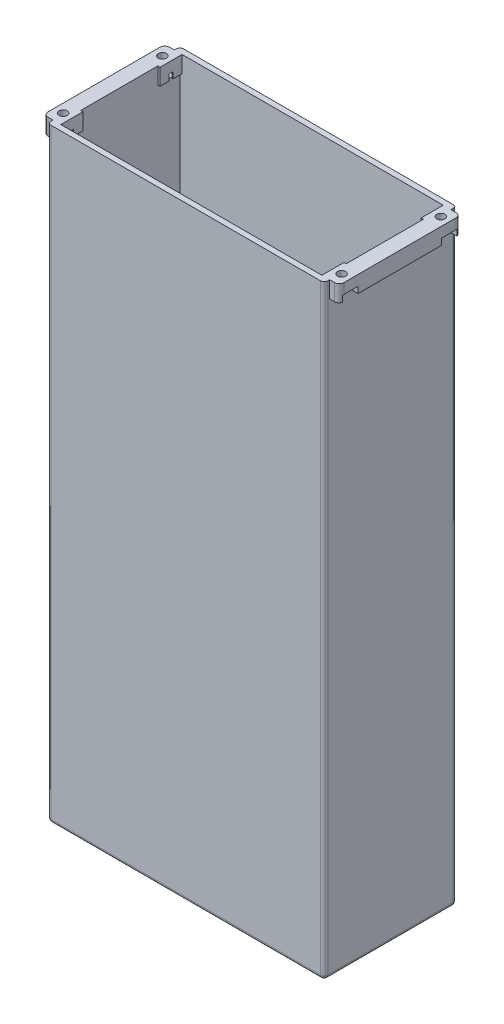
SolidWorks part; units mm, degrees
ref_plane "前视基准面" through (0, 0, 0) normal (0, 0, 1) x (1, 0, 0)
ref_plane "上视基准面" through (0, 0, 0) normal (0, 1, 0) x (1, 0, 0)
ref_plane "右视基准面" through (0, 0, 0) normal (1, 0, 0) x (0, 0, -1)
sketch "草图1" plane through (0, 0, 0) normal (0, 1, 0) x (1, 0, 0)
  line L1 (0, 0) -> (72, 0)
  line L2 (0, 0) -> (0, 32.9)
  line L3 (0, 32.9) -> (72, 32.9)
  line L4 (72, 0) -> (72, 32.9)
  dimension "D1" = 72
  dimension "D2" = 32.9
extrude "凸台-拉伸1" add sketch "草图1" along normal blind 162.5
shell "抽壳1" thickness 1.5
fillet "圆角2" radius 1 8 edges at (-1.5, 80.5, -34.4) (-1.5, 80.5, 1.5) (73.5, 80.5, 1.5) (73.5, 80.5, -34.4) (36, -1.5, 1.5) (-1.5, -1.5, -16.45) (73.5, -1.5, -16.45) (36, -1.5, -34.4)
sketch "草图2" plane through (0, 162.5, 0) normal (0, 1, 0) x (1, 0, 0)
  line L0 (0, 32.9) -> (0, 0) construction
  line L1 (-1.5, 6) -> (-1.5, 26.9)
  line L2 (-1.5, 33.4) -> (-1.5, -0.5) construction
  line L3 (0.6, 26.9) -> (-1.5, 26.9)
  line L4 (-4.1, 26.9) -> (-4.1, 6)
  line L5 (0.6, 26.9) -> (0.6, 32.9)
  line L6 (0.6, 32.9) -> (-4.1, 32.9)
  line L7 (-4.1, 26.9) -> (-4.1, 32.9)
  line L8 (0.6, 29.9) -> (-4.1, 29.9) construction
  line L9 (72, 32.9) -> (0, 32.9) construction
  line L10 (36, 0) -> (36, 32.9) construction
  line L11 (73.5, 26.9) -> (73.5, 6)
  line L12 (0, 0) -> (72, 0) construction
  line L13 (72, 16.45) -> (0, 16.45) construction
  line L14 (72, 0) -> (72, 32.9) construction
  line L15 (71.4, 32.9) -> (76.1, 32.9)
  line L16 (76.1, 26.9) -> (76.1, 32.9)
  line L17 (71.4, 26.9) -> (73.5, 26.9)
  line L18 (71.4, 26.9) -> (71.4, 32.9)
  line L19 (71.4, 6) -> (71.4, 0)
  line L20 (71.4, 6) -> (73.5, 6)
  line L21 (76.1, 6) -> (76.1, 0)
  line L22 (71.4, 0) -> (76.1, 0)
  line L23 (0.6, 0) -> (-4.1, 0)
  line L24 (-4.1, 6) -> (-4.1, 0)
  line L25 (0.6, 6) -> (-1.5, 6)
  line L26 (0.6, 6) -> (0.6, 0)
  line L27 (73.5, -0.5) -> (73.5, 33.4) construction
  line L28 (76.1, 6) -> (76.1, 26.9)
  point P30 (-1.75, 32.9)
  dimension "D2" = 4.7
  dimension "D1" = 0.6
  dimension "D3" = 6
  dimension "D4" = 3
extrude "凸台-拉伸2" add sketch "草图2" against normal blind 4.5
sketch "草图8" plane through (0, 162.5, 0) normal (0, 1, 0) x (1, 0, 0)
  line L0 (-1.5, 32.9) -> (-4.1, 32.9) construction
  line L3 (36, 32.9) -> (36, 0) construction
  line L4 (71.4, 32.9) -> (0.6, 32.9) construction
  line L5 (0.6, 0) -> (71.4, 0) construction
  line L6 (36, 16.45) -> (0, 16.45) construction
  line L7 (0, 26.9) -> (0, 6) construction
  line L8 (0.6, 26.9) -> (0.6, 32.9) construction
  line L14 (-1.75, 26.442) -> (-1.75, 33.4315) construction
  circle A0 centre (-1.75, 29.9) radius 1.1
  circle A1 centre (73.75, 29.9) radius 1.1
  circle A2 centre (73.75, 3) radius 1.1
  circle A3 centre (-1.75, 3) radius 1.1
  dimension "D1" = 2.2
  dimension "D2" = 3
  dimension "D3" = 2.35
extrude "切除-拉伸3" cut sketch "草图8" against normal blind 5
sketch "草图10" plane through (0, 158, 0) normal (0, -1, 0) x (1, 0, 0)
  line L0 (-2.3609, -27.8) -> (-4.3251, -27.8)
  line L2 (-2.4774, -32) -> (-0.5376, -32)
  line L3 (-0.5376, -32) -> (0.6749, -29.9)
  line L4 (0.6749, -29.9) -> (-0.5376, -27.8)
  line L5 (-0.5376, -27.8) -> (-2.3609, -27.8)
  line L7 (-4.0491, -30.1178) -> (-2.8944, -32.1178) [skipped]
  line L8 (-3.0882, -28.0178) -> (-4.2429, -30.0178) [skipped]
  line L9 (-4.3251, -27.8) -> (-4.3251, -32)
  line L10 (-4.3251, -32) -> (-2.4774, -32)
  line L11 (36, 0.5) -> (36, -33.4) construction
  line L12 (72.5, 0.5) -> (-0.5, 0.5) construction
  line L13 (-0.5, -33.4) -> (72.5, -33.4) construction
  line L14 (72.5, -16.45) -> (36, -16.45) construction
  line L15 (72.5, -33.4) -> (72.5, 0.5) construction
  line L16 (76.3251, -27.8) -> (76.3251, -32)
  line L17 (74.3609, -27.8) -> (76.3251, -27.8)
  line L18 (72.5376, -27.8) -> (74.3609, -27.8)
  line L19 (71.3251, -29.9) -> (72.5376, -27.8)
  line L20 (72.5376, -32) -> (71.3251, -29.9)
  line L21 (74.4774, -32) -> (72.5376, -32)
  line L22 (76.3251, -32) -> (74.4774, -32)
  line L23 (-4.3251, -5.1) -> (-4.3251, -0.9)
  line L24 (-2.3609, -5.1) -> (-4.3251, -5.1)
  line L25 (-0.5376, -5.1) -> (-2.3609, -5.1)
  line L26 (0.6749, -3) -> (-0.5376, -5.1)
  line L27 (-0.5376, -0.9) -> (0.6749, -3)
  line L28 (-2.4774, -0.9) -> (-0.5376, -0.9)
  line L29 (-4.3251, -0.9) -> (-2.4774, -0.9)
  line L30 (74.3609, -5.1) -> (76.3251, -5.1)
  line L31 (72.5376, -5.1) -> (74.3609, -5.1)
  line L32 (71.3251, -3) -> (72.5376, -5.1)
  line L33 (72.5376, -0.9) -> (71.3251, -3)
  line L34 (74.4774, -0.9) -> (72.5376, -0.9)
  line L35 (76.3251, -0.9) -> (74.4774, -0.9)
  line L36 (76.3251, -5.1) -> (76.3251, -0.9)
  circle A0 centre (-1.75, -29.9) radius 2.1 construction
  dimension "D1" = 4.2
  dimension "D2" = 5
extrude "切除-拉伸4" cut sketch "草图10" against normal blind 1.7
fillet "圆角3" radius 1.25 4 edges at (76.1, 160.25, -32.9) (76.1, 160.25, 0) (-4.1, 160.25, 0) (-4.1, 160.25, -32.9)
sketch "草图11" plane through (0, 158, 0) normal (0, -1, 0) x (1, 0, 0)
  line L0 (0.6, -3) -> (0.9666, -3) construction
  line L1 (0.3, -2.5) -> (0.8, -2.5)
  line L2 (0.3, -2.5) -> (0.3, -3.5)
  line L3 (0.3, -3.5) -> (0.8, -3.5)
  line L4 (0.8, -2.5) -> (0.8, -3.5)
  line L5 (0.6, -3.1297) -> (0.6, -2.8703) construction
  line L6 (0.6, -3.1297) -> (0.6, -6) construction
  line L7 (36, 0) -> (36, -32.9) construction
  line L8 (0.6, 0) -> (71.4, 0) construction
  line L9 (71.4, -32.9) -> (0.6, -32.9) construction
  line L10 (0, -16.45) -> (72, -16.45) construction
  line L11 (0, -26.9) -> (0, -6) construction
  line L12 (72, -6) -> (72, -26.9) construction
  line L13 (71.7, -3.5) -> (71.2, -3.5)
  line L14 (71.2, -2.5) -> (71.2, -3.5)
  line L15 (71.7, -2.5) -> (71.2, -2.5)
  line L16 (71.7, -2.5) -> (71.7, -3.5)
  line L17 (71.7, -30.4) -> (71.7, -29.4)
  line L18 (71.7, -30.4) -> (71.2, -30.4)
  line L19 (71.2, -30.4) -> (71.2, -29.4)
  line L20 (71.7, -29.4) -> (71.2, -29.4)
  line L21 (0.3, -29.4) -> (0.8, -29.4)
  line L22 (0.8, -30.4) -> (0.8, -29.4)
  line L23 (0.3, -30.4) -> (0.8, -30.4)
  line L24 (0.3, -30.4) -> (0.3, -29.4)
  dimension "D1" = 0.5
  dimension "D2" = 1
  dimension "D3" = 0.2
extrude "切除-拉伸5" cut sketch "草图11" against normal blind 1.7
fillet "圆角4" radius 0.2 7 edges at (0, 158, -5.0845) (72, 158, -27.8155) (72, 158, -31.9845) (72, 158, -5.0845) (0, 158, -31.9845) (0, 158, -27.8155) (0, 158, -0.9155)
fillet "圆角5" radius 0.1 8 edges at (0, 157.9, -28.7311) (0, 157.9, -31.0689) (0, 157.9, -4.1689) (0, 157.9, -1.8311) (72, 157.9, -4.1689) (72, 157.9, -1.8311) (72, 157.9, -28.7311) (72, 157.9, -31.0689)
